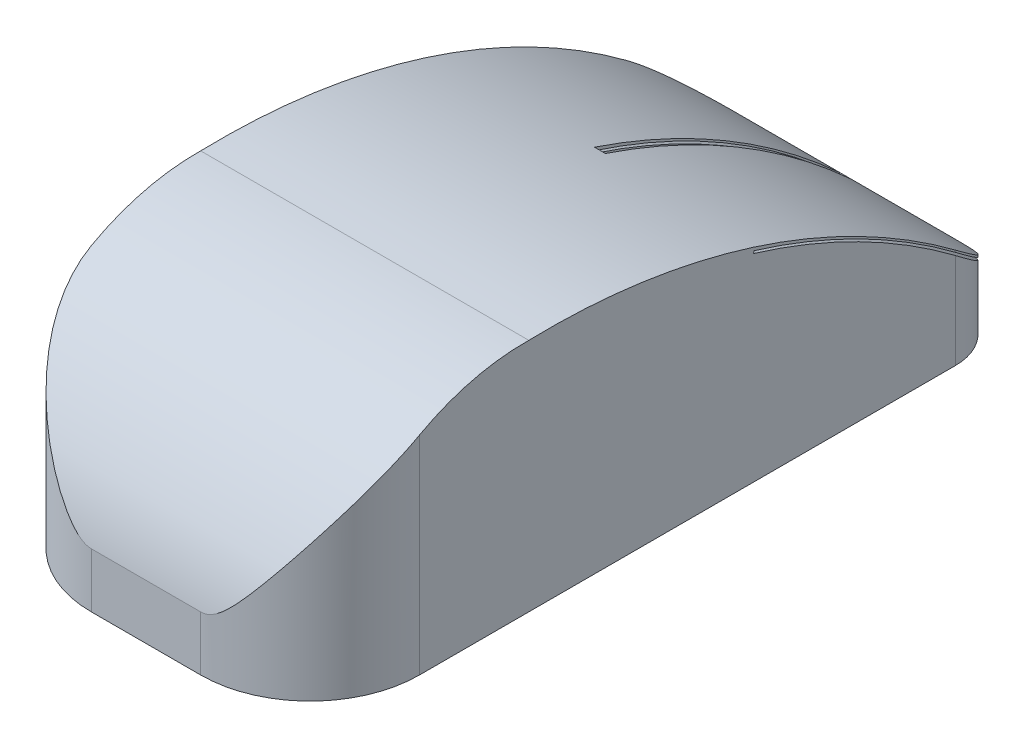
SolidWorks part; units mm, degrees
ref_plane "Front Plane" through (0, 0, 0) normal (0, 0, 1) x (1, 0, 0)
ref_plane "Top Plane" through (0, 0, 0) normal (0, 1, 0) x (1, 0, 0)
ref_plane "Right Plane" through (0, 0, 0) normal (1, 0, 0) x (0, 0, -1)
sketch "Sketch1" plane through (0, 0, 0) normal (0, 1, 0) x (1, 0, 0)
  line L0 (0, 20) -> (0, 118)
  line L1 (10, 128) -> (50, 128)
  line L2 (60, 118) -> (60, 20)
  line L3 (40, 0) -> (20, 0)
  arc A0 (0, 118) -> (10, 128) centre (10, 118) cw
  arc A1 (50, 128) -> (60, 118) centre (50, 118) cw
  arc A2 (60, 20) -> (40, 0) centre (40, 20) cw
  arc A3 (0, 20) -> (20, 0) centre (20, 20) ccw
  point P7 (0, 128)
  point P10 (60, 128)
  point P15 (0, 0)
  dimension "D3" = 10
  dimension "D4" = 20
  dimension "D1" = 128
  dimension "D2" = 60
extrude "Boss-Extrude1" add sketch "Sketch1" along normal blind 10
sketch "Sketch2" plane through (0, 0, 0) normal (1, 0, 0) x (0, 0, -1)
  line L0 (0, 10) -> (40, 10) construction
  line L1 (20, 10) -> (118, 10) construction
  line L2 (40, 10) -> (40, 43) construction
  line L3 (0, 10) -> (128, 10)
  arc A0 (0, 10) -> (40, 43) centre (39.3836, 3.0047) cw
  arc A1 (40, 43) -> (128, 10) centre (43.3291, -81.9557) cw
  dimension "D3" = 40
  dimension "D4" = 125
  dimension "D1" = 40
  dimension "D2" = 33
extrude "Boss-Extrude2" add sketch "Sketch2" along normal blind 60
extrude "Cut-Extrude1" cut sketch "Sketch1<2>" along normal blind 60 flip side to cut
sketch "Sketch1<2>" plane through (0, 0, 0) normal (0, 1, 0) x (1, 0, 0) same geometry as "Sketch1"
sketch "Sketch3" plane through (60, 0, 0) normal (1, 0, 0) x (0, 0, -1)
sketch "Sketch4" plane through (0, 0, 0) normal (-1, 0, 0) x (0, 0, 1)
  line L0 (-128, 10) -> (-128, 9) construction
  line L1 (-128, 10) -> (-128, 0) construction
  line L2 (-81.079, 37.2079) -> (-81.079, 36.2079) construction
  arc A1 (-40, 43) -> (-118, 18.2903) centre (-43.3291, -81.9557) ccw construction
  arc A2 (-81.079, 36.2079) -> (-128, 9) centre (-46.308, -77.8185) ccw
  dimension "D1" = 1
  dimension "D2" = 1
extrude "Cut-Extrude-Thin1" cut sketch "Sketch4" against normal blind 60 and the other way through all thin thin type one direction wall 0.4
sketch "Sketch5" plane through (0, 0, -128) normal (0, 0, -1) x (-1, 0, 0)
  line L0 (-30, 0) -> (-30, 10) construction
  line L1 (-50, 0) -> (-10, 0) construction
  line L2 (-50, 10) -> (-10, 10) construction
  line L3 (-29, 10) -> (-31, 10)
  line L4 (-31, 10) -> (-31, 43)
  line L5 (-60, 43) -> (0, 43) construction
  line L6 (-29, 10) -> (-29, 43)
  line L7 (-31, 43) -> (-29, 43)
  dimension "D1" = 1
extrude "Cut-Extrude2" cut sketch "Sketch5" against normal blind 45
